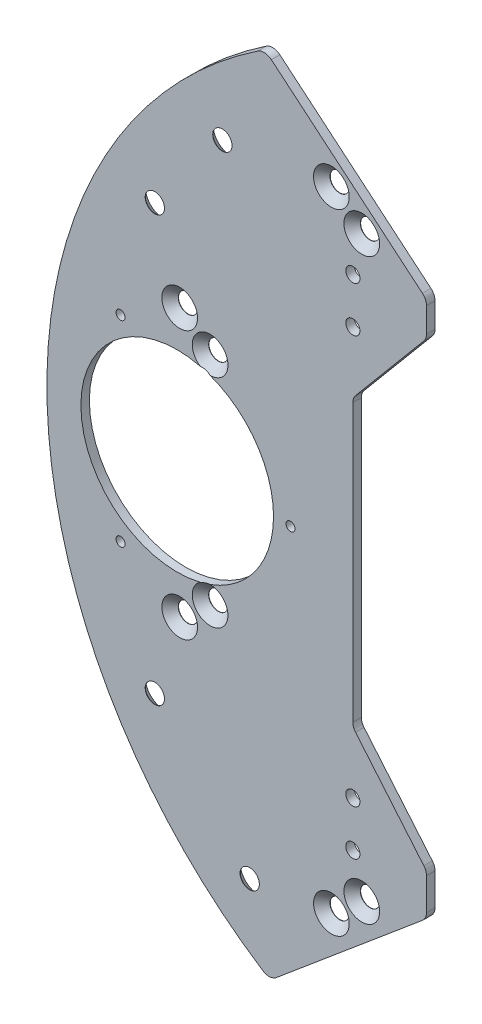
SolidWorks part; units mm, degrees
ref_plane "Plano frontal" through (0, 0, 0) normal (0, 0, 1) x (1, 0, 0)
ref_plane "Plano superior" through (0, 0, 0) normal (0, 1, 0) x (1, 0, 0)
ref_plane "Plano direito" through (0, 0, 0) normal (1, 0, 0) x (0, 0, -1)
sketch "Esboço1" plane through (0, 0, 0) normal (0, 0, 1) x (1, 0, 0)
  line L0 (-17, 85.3229) -> (-17, -85.3229)
  arc A0 (-17, 85.3229) -> (-17, -85.3229) centre (0, 0) ccw
  dimension "D1" = 174
  dimension "D2" = 17
extrude "Ressalto-extrusão1" add sketch "Esboço1" along normal blind 1.5
sketch "Esboço2" plane through (0, 0, 1.5) normal (0, 0, 1) x (1, 0, 0)
  line L0 (0, 0) -> (-61, 0) construction
  line L1 (-61, 0) -> (-41, 0) construction
  line L2 (-61, 0) -> (-71, 17.3205) construction
  line L3 (-61, 0) -> (-71, -17.3205) construction
  circle A0 centre (-61, 0) radius 17
  point P4 (-41, 0)
  dimension "D2" = 34
  dimension "D1" = 61
  dimension "D3" = 20
  dimension "D4" = 120
  dimension "D5" = 120
  dimension "D6" = 20
  dimension "D7" = 20
extrude "Corte-extrusão1" cut sketch "Esboço2" against normal blind 1.5
hole_wizard "Furo roscado de M21" positions "3DSketch1" profile "Esboço3" tap size "M2" standard "ISO" end condition up to next
sketch3d "3DSketch1"
  point P0 (-71, 17.3205, 1.5)
  point P3 (-41, 0, 1.5)
  point P10 (-71, -17.3205, 1.5)
sketch "Esboço3" plane through (-71, 17.3205, 1.5) normal (1, 0, 0) x (0, -1, 0)
  line L0 (0, 0) -> (0, 1.5)
  line L1 (0, 1.5) -> (0.8, 1.5)
  line L2 (0.8, 1.5) -> (0.8, 0)
  line L5 (0.8, 0) -> (0, 0)
  line L11 (0, -6.35) -> (0, 107.95) construction
  dimension "Thru Tap Drill Dia." = 1.6
  dimension "Thru Tap Drill Depth" = 1.5
cosmetic thread "Rosca de furo1" parameters "D2"=2
cosmetic thread "Rosca de furo2" parameters "D2"=2
cosmetic thread "Rosca de furo3" parameters "D2"=2
sketch "Esboço6" plane through (0, 0, 1.5) normal (0, 0, 1) x (1, 0, 0)
  line L0 (0, 0) -> (-61, 0) construction
  line L1 (0, 0) -> (-66.6459, 55.9225) construction
  line L2 (0, 0) -> (-66.6459, -55.9225) construction
  line L3 (-30, -24.445) -> (-30, 24.445)
  line L4 (-29.5321, 25.7306) -> (-17, 40.6658)
  line L5 (-29.5321, -25.7306) -> (-17, -40.6658)
  line L6 (-17, 40.6658) -> (-17, -40.6658)
  line L7 (-17, -85.3229) -> (-17, 85.3229) construction
  arc A0 (-17, 85.3229) -> (-17, -85.3229) centre (0, 0) ccw construction
  arc A1 (-30, -24.445) -> (-29.5321, -25.7306) centre (-28, -24.445) ccw
  arc A2 (-30, 24.445) -> (-29.5321, 25.7306) centre (-28, 24.445) cw
  point P4 (-30, 0)
  point P13 (-30, 0)
  point P21 (-30, 25.173)
  dimension "D4" = 2
  dimension "D1" = 40
  dimension "D2" = 40
  dimension "D3" = 30
extrude "Corte-extrusão3" cut sketch "Esboço6" against normal blind 1.5
sketch "Esboço7" plane through (0, 0, 1.5) normal (0, 0, 1) x (1, 0, 0)
  line L0 (0, 0) -> (0, 87) construction
  line L1 (-17, 80) -> (0, 80) construction
  line L2 (-17, 40.6658) -> (-17, 85.3229) construction
  line L3 (-27.5, 80) -> (-34.1906, 80)
  line L4 (-34.1906, 80) -> (-34.1906, 87)
  line L5 (-34.1906, 87) -> (-17, 87)
  line L6 (-27.5, 80) -> (-27.5, 55)
  line L7 (-27.5, 55) -> (-17, 55)
  line L8 (-17, 55) -> (-17, 87)
  line L9 (-17, 80) -> (-27.5, 80) construction
  line L10 (-17, 55) -> (0, 55) construction
  line L11 (-17, 87) -> (0, 87) construction
  arc A0 (-17, 85.3229) -> (-17, -85.3229) centre (0, 0) ccw construction
  point P3 (0, 80)
  dimension "D1" = 87
  dimension "D2" = 80
  dimension "D3" = 25
  dimension "D4" = 27.5
sketch "Esboço9" plane through (0, 0, 1.5) normal (0, 0, 1) x (1, 0, 0)
  line L0 (0, 0) -> (-66.6459, 55.9225) construction
  line L1 (0, 0) -> (-62.0797, 0) construction
  line L2 (0, 0) -> (-66.6459, -55.9225) construction
  line L3 (-80.0319, 39.9696) -> (-53.2598, 71.8754) construction
  line L4 (-77.3347, 37.7064) -> (-50.5626, 69.6122) construction
  line L5 (-80.0319, 39.9696) -> (-77.3347, 37.7064) construction
  line L6 (-50.5626, 69.6122) -> (-53.2598, 71.8754) construction
  line L7 (-77.3347, 37.7064) -> (-60.5583, 23.6294) construction
  line L8 (-50.5626, 69.6122) -> (-33.7862, 55.5351) construction
  line L9 (-60.5583, 23.6294) -> (-55.196, 19.1299) construction
  line L10 (-33.7862, 55.5351) -> (-28.4239, 51.0356) construction
  line L11 (-80.0319, -39.9696) -> (-53.2598, -71.8754) construction
  line L12 (-53.2598, -71.8754) -> (-50.5626, -69.6122) construction
  line L13 (-50.5626, -69.6122) -> (-77.3347, -37.7064) construction
  line L14 (-77.3347, -37.7064) -> (-80.0319, -39.9696) construction
  line L15 (-77.3347, -37.7064) -> (-55.196, -19.1299) construction
  line L16 (-50.5626, -69.6122) -> (-28.4239, -51.0356)
  line L17 (-80.0319, -39.9696) -> (-82.3942, -37.1544) construction
  line L18 (-53.2598, -71.8754) -> (-50.8976, -74.6906) construction
  line L19 (-50.8976, -74.6906) -> (-48.2004, -72.4274) construction
  line L20 (-48.2004, -72.4274) -> (-50.5626, -69.6122) construction
  line L21 (-82.3942, -37.1544) -> (-79.697, -34.8912) construction
  line L22 (-79.697, -34.8912) -> (-77.3347, -37.7064) construction
  line L23 (-80.0319, 39.9696) -> (-82.3942, 37.1544) construction
  line L24 (-82.3942, 37.1544) -> (-79.697, 34.8912) construction
  line L25 (-79.697, 34.8912) -> (-77.3347, 37.7064) construction
  line L26 (-53.2598, 71.8754) -> (-50.8976, 74.6906) construction
  line L27 (-50.8976, 74.6906) -> (-48.2004, 72.4274) construction
  line L28 (-48.2004, 72.4274) -> (-50.5626, 69.6122) construction
  arc A0 (-17, 85.3229) -> (-17, -85.3229) centre (0, 0) ccw construction
  point P11 (-66.6459, 55.9225)
  point P14 (-63.9487, 53.6593)
  point P15 (-33.7862, -55.5351)
  point P21 (-66.6459, -55.9225)
  point P26 (-60.5583, -23.6294)
  dimension "D1" = 40
  dimension "D2" = 40
  dimension "D3" = 49
  dimension "D5" = 21.9
  dimension "D6" = 7
  dimension "D7" = 7
  dimension "D8" = 49
  dimension "D9" = 21.9
  dimension "D10" = 7
  dimension "D11" = 21.9
  dimension "D12" = 7
  dimension "D13" = 41.65
  dimension "D14" = 41.65
hole_wizard "Escareado para parafuso com cabeça escareada chata de M31" positions "3DSketch3" profile "Esboço11" countersink size "M3" standard "ISO" end condition up to next
sketch3d "3DSketch3"
  point P0 (-60.5583, -23.6294, 1.5)
  point P3 (-55.196, -19.1299, 1.5)
  point P6 (-28.4239, -51.0356, 1.5)
  point P9 (-33.7862, -55.5351, 1.5)
  point P12 (-33.7862, 55.5351, 1.5)
  point P15 (-28.4239, 51.0356, 1.5)
  point P18 (-60.5583, 23.6294, 1.5)
  point P21 (-55.196, 19.1299, 1.5)
sketch "Esboço11" plane through (-60.5583, -23.6294, 1.5) normal (1, 0, 0) x (0, -1, 0)
  line L0 (0, 0) -> (0, 1.5)
  line L1 (0, 1.5) -> (1.7, 1.5)
  line L2 (1.7, 1.5) -> (1.7, 1.45)
  line L3 (1.7, 1.45) -> (3.15, 0)
  line L5 (3.15, 0) -> (0, 0)
  line L6 (-1.7, 1.45) -> (-3.15, 0) construction
  line L11 (0, -6.35) -> (0, 107.95) construction
  dimension "Thru Hole Dia." = 3.4
  dimension "Thru Hole Depth" = 1.5
  dimension "Near C'Sink Dia." = 6.3
  dimension "Near C'Sink Angle" = 90
sketch "Esboço13" plane through (0, 0, 0) normal (0, 0, -1) x (-1, 0, 0)
  line L0 (0, 0) -> (64.9519, 37.5) construction
  line L1 (0, 0) -> (64.9519, -37.5) construction
  line L2 (0, 0) -> (48.2091, -57.4533) construction
  line L3 (0, 0) -> (53.033, 53.033) construction
  line L4 (0, 0) -> (78, 0) construction
  circle A1 centre (61, 0) radius 17 construction
  dimension "D1" = 45
  dimension "D2" = 50
  dimension "D5" = 75
  dimension "D7" = 30
  dimension "D8" = 30
hole_wizard "Escareado para parafuso com cabeça escareada chata de M32" positions "3DSketch6" profile "Esboço16" countersink size "M3" standard "ISO"
sketch3d "3DSketch6"
  point P0 (-48.2091, -57.4533, 0)
  point P3 (-64.9519, -37.5, 0)
  point P6 (-64.9519, 37.5, 0)
  point P9 (-53.033, 53.033, 0)
sketch "Esboço16" plane through (-48.2091, -57.4533, 0) normal (1, 0, 0) x (0, 1, 0)
  line L0 (0, 0) -> (0, 8.2715)
  line L1 (0, 8.2715) -> (1.7, 7.25)
  line L2 (1.7, 7.25) -> (1.7, 1.45)
  line L3 (1.7, 1.45) -> (3.15, 0)
  line L5 (3.15, 0) -> (0, 0)
  line L6 (-1.7, 1.45) -> (-3.15, 0) construction
  line L10 (0, 8.2715) -> (-1.7, 7.25) construction
  line L11 (0, -6.35) -> (0, 107.95) construction
  dimension "Hole Dia." = 3.4
  dimension "Hole Depth" = 7.25
  dimension "Near C'Sink Dia." = 6.3
  dimension "Near C'Sink Angle" = 90
  dimension "Drill Angle" = 118
sketch "Esboço17" plane through (0, 0, 0) normal (0, 0, -1) x (-1, 0, 0)
  line L0 (0, 0) -> (44, 0) construction
  line L1 (0, 0) -> (41.0122, 41.0122) construction
  line L7 (19.799, 41.0122) -> (41.0122, 19.799) construction
  circle A0 centre (61, 0) radius 17 construction
  point P11 (30.4056, 30.4056)
  dimension "D1" = 45
  dimension "D2" = 58
  dimension "D3" = 30
  dimension "D4" = 15
sketch "Esboço19" plane through (0, 0, 0) normal (0, 0, -1) x (-1, 0, 0)
  line L0 (28.4239, 51.0356) -> (33.7862, 55.5351) construction
  line L1 (33.7862, 55.5351) -> (31.2151, 58.5993) construction
  line L2 (31.2151, 58.5993) -> (17, 46.6714)
  line L3 (17, 40.6658) -> (17, 85.3229) construction
  line L4 (17, 46.6714) -> (17, 85.3229)
  line L5 (17, 85.3229) -> (63.063, 85.3229)
  line L6 (63.063, 85.3229) -> (31.2151, 58.5993)
  line L7 (28.4239, -51.0356) -> (33.7862, -55.5351) construction
  line L8 (33.7862, -55.5351) -> (30.5723, -59.3653) construction
  line L9 (30.5723, -59.3653) -> (17, -47.9768)
  line L10 (17, -85.3229) -> (17, -40.6658) construction
  line L11 (17, -47.9768) -> (17, -85.3229)
  line L12 (17, -85.3229) -> (61.5073, -85.3229)
  line L13 (61.5073, -85.3229) -> (30.5723, -59.3653)
  dimension "D1" = 4
  dimension "D2" = 5
extrude "Corte-extrusão7" cut sketch "Esboço19" against normal through all
sketch "Esboço20" plane through (0, 0, 0) normal (0, 0, -1) x (-1, 0, 0)
  line L0 (17, 46.6714) -> (47.9179, 72.6146) construction
  line L1 (17, -47.9768) -> (47.042, -73.1851) construction
  line L2 (47.9179, 72.6146) -> (45.5162, 70.5994)
  line L3 (44.6312, -71.1622) -> (47.042, -73.1851)
  arc A0 (47.042, -73.1851) -> (47.9179, 72.6146) centre (0, 0) ccw
  arc A1 (44.6312, -71.1622) -> (45.5162, 70.5994) centre (0, 0) ccw
  dimension "D1" = 84
extrude "Corte-extrusão8" cut sketch "Esboço20" against normal through all
fillet "Filete1" radius 2 6 edges at (-45.5162, 70.5994, 0.75) (-17, 46.6714, 0.75) (-17, 40.6658, 0.75) (-44.6312, -71.1622, 0.75) (-17, -40.6658, 0.75) (-17, -47.9768, 0.75)
sketch "Esboço22" plane through (0, 0, 1.5) normal (0, 0, 1) x (1, 0, 0)
  line L0 (0, 0) -> (-83.9983, -0.5343) construction
  line L1 (0, 0) -> (0, 40) construction
  line L2 (0, 40) -> (-30, 40) construction
  line L3 (-30, 36) -> (-30, 44)
  line L4 (0, 0) -> (0, -40) construction
  line L5 (0, -40) -> (-30, -40) construction
  line L6 (-30, -44) -> (-30, -36)
  arc A0 (-46.7752, 69.7717) -> (-45.8838, -70.361) centre (0, 0) ccw construction
  point P11 (-30, 40)
  point P16 (-30, -40)
  dimension "D1" = 40
  dimension "D2" = 30
  dimension "D3" = 8
  dimension "D4" = 40
  dimension "D5" = 30
  dimension "D6" = 8
hole_wizard "Broca de rosquear para tarraxa de M31" positions "3DSketch7" profile "Esboço23" hole size "M3" standard "ISO" end condition through all
sketch3d "3DSketch7"
  point P0 (-30, -44, 1.5)
  point P3 (-30, -36, 1.5)
  point P6 (-30, 44, 1.5)
  point P9 (-30, 36, 1.5)
sketch "Esboço23" plane through (-30, -44, 1.5) normal (1, 0, 0) x (0, -1, 0)
  line L0 (0, 0) -> (0, 1.5)
  line L1 (0, 1.5) -> (1.25, 1.5)
  line L2 (1.25, 1.5) -> (1.25, 0)
  line L5 (1.25, 0) -> (0, 0)
  line L11 (0, -6.35) -> (0, 107.95) construction
  dimension "Thru Hole Dia." = 2.5
  dimension "Thru Hole Depth" = 1.5
